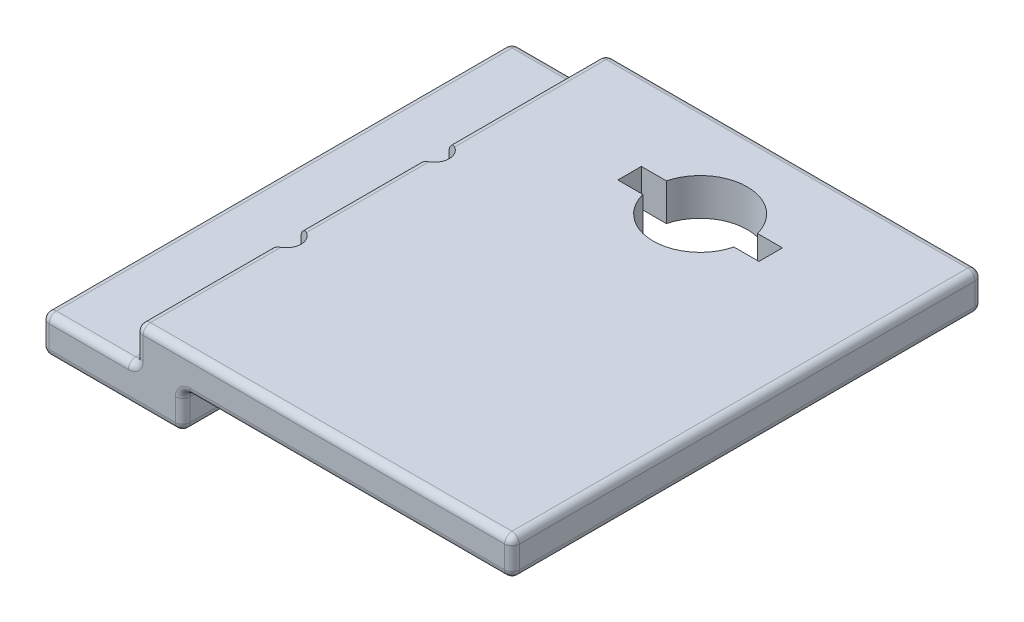
SolidWorks part; units mm, degrees
ref_plane "Front Plane" through (0, 0, 0) normal (0, 0, 1) x (1, 0, 0)
ref_plane "Top Plane" through (0, 0, 0) normal (0, 1, 0) x (1, 0, 0)
ref_plane "Right Plane" through (0, 0, 0) normal (1, 0, 0) x (0, 0, -1)
sketch "Sketch1" plane through (0, 0, 0) normal (0, 0, 1) x (1, 0, 0)
  line L1 (-31.75, 5) -> (31.75, 5)
  line L2 (-31.75, 5) -> (-31.75, -5)
  line L3 (-31.75, -5) -> (31.75, -5)
  line L4 (31.75, 5) -> (31.75, -5)
  line L5 (-31.75, 5) -> (31.75, -5) construction
  line L6 (-31.75, -5) -> (31.75, 5) construction
  point P0 (0, 0)
  dimension "D1" = 10
  dimension "D2" = 63.5
extrude "Boss-Extrude1" add sketch "Sketch1" along normal blind 63.5
sketch "Sketch2" plane through (0, 5, 0) normal (0, 1, 0) x (1, 0, 0)
  line L0 (31.75, -63.5) -> (-31.75, -63.5) construction
  line L1 (-31.75, 0) -> (-19.05, 0)
  line L2 (-31.75, 0) -> (-31.75, -63.5)
  line L3 (-31.75, -63.5) -> (-19.05, -63.5)
  line L4 (-19.05, 0) -> (-19.05, -63.5)
  dimension "D1" = 12.7
extrude "Cut-Extrude1" cut sketch "Sketch2" against normal offset from surface (5 mm away) 5 up to face at (0, -5, 31.75)
sketch "Sketch3" plane through (0, -5, 0) normal (0, -1, 0) x (1, 0, 0)
  line L0 (-31.75, 0) -> (31.75, 0) construction
  line L1 (31.75, 63.5) -> (-12.7, 63.5)
  line L2 (31.75, 63.5) -> (31.75, 0)
  line L3 (31.75, 0) -> (-12.7, 0)
  line L4 (-12.7, 63.5) -> (-12.7, 0)
  line L5 (-31.75, 63.5) -> (-31.75, 0) construction
  dimension "D1" = 19.05
extrude "Cut-Extrude2" cut sketch "Sketch3" against normal blind 5
sketch "Sketch4" plane through (0, 5, 0) normal (0, 1, 0) x (1, 0, 0)
  line L0 (6.35, 0) -> (6.35, -63.5) construction
  line L1 (31.75, -63.5) -> (-19.05, -63.5) construction
  line L2 (31.75, 0) -> (-19.05, 0) construction
  circle A0 centre (6.35, -12.7) radius 6.35
  dimension "D1" = 12.7
  dimension "D2" = 12.7
extrude "Cut-Extrude3" cut sketch "Sketch4" against normal blind 5
sketch "Sketch5" plane through (0, 0, 0) normal (0, -1, 0) x (1, 0, 0)
  line L1 (-3.175, 14.2875) -> (15.875, 14.2875)
  line L2 (-3.175, 14.2875) -> (-3.175, 11.1125)
  line L3 (-3.175, 11.1125) -> (15.875, 11.1125)
  line L4 (15.875, 14.2875) -> (15.875, 11.1125)
  line L5 (-3.175, 14.2875) -> (15.875, 11.1125) construction
  line L6 (-3.175, 11.1125) -> (15.875, 14.2875) construction
  point P0 (6.35, 12.7)
  dimension "D1" = 19.05
  dimension "D2" = 3.175
extrude "Cut-Extrude4" cut sketch "Sketch5" against normal blind 5
sketch "Sketch6" plane through (0, 0, 0) normal (0, 1, 0) x (1, 0, 0)
  line L0 (-31.75, 0) -> (-19.05, 0) construction
  line L1 (-31.75, -63.5) -> (-31.75, 0) construction
  circle A0 centre (-19.05, -43.18) radius 2
  circle A1 centre (-19.05, -23.18) radius 2
  dimension "D3" = 4
  dimension "D1" = 43.18
  dimension "D2" = 20
  dimension "D4" = 12.7
extrude "Cut-Extrude5" cut sketch "Sketch6" along normal through all
sketch "Sketch7" plane through (0, 0, 0) normal (0, 1, 0) x (1, 0, 0)
  circle A0 centre (-19.05, -23.18) radius 1.65
  circle A1 centre (-19.05, -43.18) radius 1.65
  dimension "D1" = 3.3
extrude "Cut-Extrude6" cut sketch "Sketch7" against normal through all
fillet "Fillet1" radius 1 28 edges at (-31.75, -5, 31.75) (-31.75, 0, 31.75) (31.75, 5, 31.75) (31.75, 0, 31.75) (31.75, 2.5, 0) (6.35, 5, 0) (-19.05, 2.5, 0) (-25.4, 0, 0) (-31.75, -2.5, 0) (-22.225, -5, 0) (9.525, 0, 0) (-22.225, -5, 63.5) (-31.75, -2.5, 63.5) (-25.4, 0, 63.5) (-19.05, 2.5, 63.5) (6.35, 5, 63.5) (31.75, 2.5, 63.5) (9.525, 0, 63.5) (-12.7, -2.5, 63.5) (-12.7, 0, 31.75) (-12.7, -2.5, 0) (-12.7, -5, 31.75) (-19.05, 0, 10.59) (-19.05, 5, 33.18) (-19.05, 0, 33.18) (-19.05, 0, 54.34) (-19.05, 5, 54.34) (-19.05, 5, 10.59)
